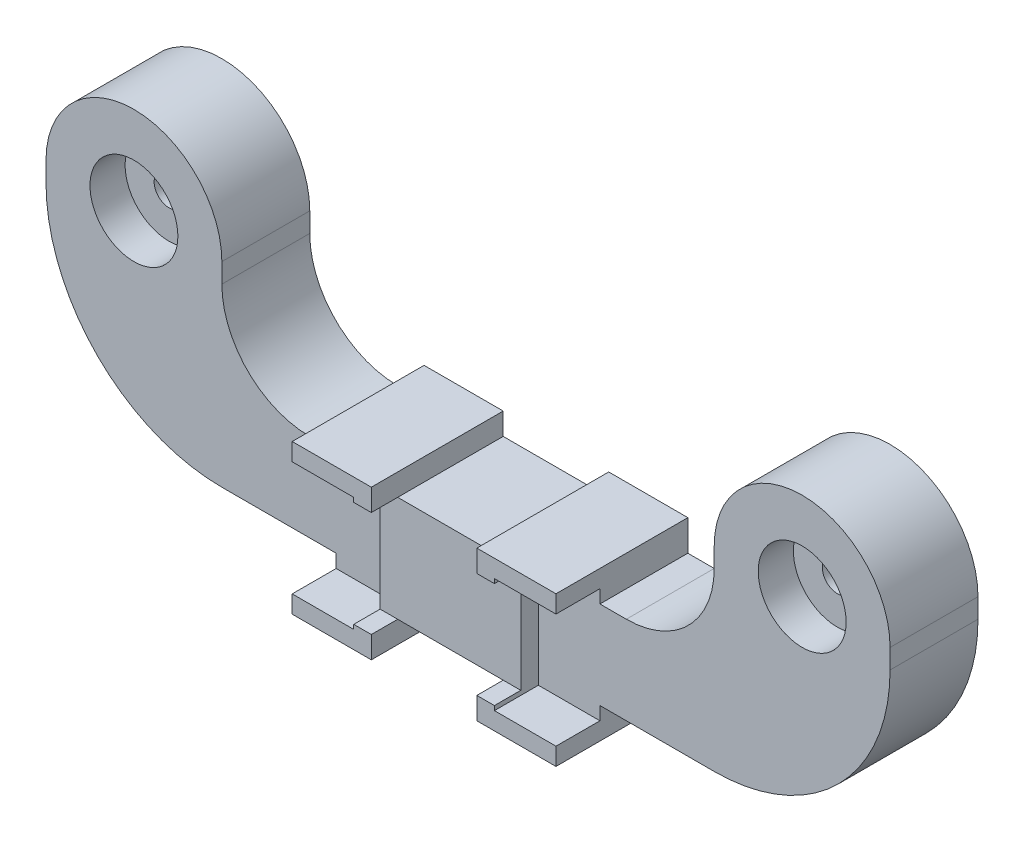
SolidWorks part; units mm, degrees
material "PETG"
ref_plane "Front Plane" through (0, 0, 0) normal (0, 0, 1) x (1, 0, 0)
ref_plane "Top Plane" through (0, 0, 0) normal (0, 1, 0) x (1, 0, 0)
ref_plane "Right Plane" through (0, 0, 0) normal (1, 0, 0) x (0, 0, -1)
sketch "Sketch1" plane through (0, 0, 0) normal (0, 0, 1) x (1, 0, 0)
  line L0 (-48, 20) -> (-48, 22.22)
  line L1 (28, 0) -> (-28, 0)
  line L2 (0, 0) -> (0, 10)
  line L3 (18, 10) -> (-18, 10)
  line L5 (0, 0.8051) -> (0, 50000.8051) construction
  line L6 (-28, 22.22) -> (-28, 20)
  line L7 (28, 22.22) -> (28, 20)
  line L8 (48, 20) -> (48, 22.22)
  circle A0 centre (-38, 22.22) radius 1.7
  arc A1 (-28, 22.22) -> (-48, 22.22) centre (-38, 22.22) ccw
  arc A2 (-18, 10) -> (-28, 20) centre (-18, 20) cw
  arc A3 (-28, 0) -> (-48, 20) centre (-28, 20) cw
  arc A4 (28, 0) -> (48, 20) centre (28, 20) ccw
  arc A5 (18, 10) -> (28, 20) centre (18, 20) ccw
  arc A6 (28, 22.22) -> (48, 22.22) centre (38, 22.22) cw
  circle A7 centre (38, 22.22) radius 1.7
  circle A8 centre (-38, 22.22) radius 5
  circle A9 centre (38, 22.22) radius 5
  dimension "D1" = 38
  dimension "D2" = 3.4
  dimension "D5" = 20
  dimension "D7" = 10
  dimension "D8" = 20
  dimension "D6" = 10
  dimension "D3" = 22.22
  dimension "D4" = 10
extrude "Boss-Extrude1" add sketch "Sketch1" against normal blind 10 contours A3 L1 L2 L3 A2 L6 A1 L0 A8 | A8 A0 | A6 L7 A5 L3 L2 L1 A4 L8 A9 | A9 A7 region at (-27.9027, 11.6824, 0) region at (27.9027, 11.6824, 0) region at (-42.8586, 22.22, 0) region at (33.1414, 22.22, 0)
extrude "Cut-Extrude1" cut sketch "Sketch1<4>" against normal blind 4 contours A8 A0 | A9 A7 region at (-42.8586, 22.22, 0) region at (33.1414, 22.22, 0)
sketch "Sketch1<4>" plane through (0, 0, 0) normal (0, 0, 1) x (1, 0, 0) same geometry as "Sketch1"
sketch "Sketch3" plane through (0, 0, 0) normal (0, 0, 1) x (1, 0, 0)
  line L0 (-6, 11.005) -> (-6, -3.505)
  line L5 (-15, 11.505) -> (-8, 11.505)
  line L6 (-15, 11.505) -> (-15, -1.505)
  line L7 (-15, -1.505) -> (-8, -1.505)
  line L8 (-8, 11.505) -> (-8, -1.505)
  line L10 (-15, 11.505) -> (-15, 13.505)
  line L11 (-15, 13.505) -> (-6, 13.505)
  line L12 (-6, 11.005) -> (-6, 13.505)
  line L14 (-15, -1.505) -> (-15, -3.505)
  line L15 (-15, -3.505) -> (-6, -3.505)
  line L17 (-6, -1.005) -> (-8, -1.005)
  line L18 (-6, 11.005) -> (6, 11.005)
  line L19 (-6, 11.005) -> (-6, -1.005)
  line L20 (-6, -1.005) -> (6, -1.005)
  line L21 (0, 11.005) -> (0, -1.005)
  line L22 (0, 0) -> (0, 50000) construction
  line L23 (-6, 11.005) -> (-8, 11.005)
  line L24 (28, 0) -> (-28, 0) construction
  line L25 (6, 11.005) -> (8, 11.005)
  line L26 (6, 11.005) -> (6, -1.005)
  line L27 (6, -1.005) -> (8, -1.005)
  line L28 (15, -3.505) -> (6, -3.505)
  line L29 (15, -1.505) -> (15, -3.505)
  line L30 (6, 11.005) -> (6, 13.505)
  line L31 (15, 13.505) -> (6, 13.505)
  line L32 (15, 11.505) -> (15, 13.505)
  line L33 (8, 11.505) -> (8, -1.505)
  line L34 (15, -1.505) -> (8, -1.505)
  line L35 (15, 11.505) -> (15, -1.505)
  line L36 (15, 11.505) -> (8, 11.505)
  line L37 (6, 11.005) -> (6, -3.505)
  point P13 (0, 5)
  point P20 (0, 0)
  line M5 (-28, 0) -> (28, 0)
  line M11 (18, 10) -> (-18, 10)
  dimension "D1" = 15
  dimension "D2" = 13.01
  dimension "D3" = 5
  dimension "D4" = 2
  dimension "D5" = 0.5
  dimension "D6" = 0.5
  dimension "D7" = 7
extrude "Boss-Extrude2" add sketch "Sketch3" against normal through all contours L21 L18 L0 M11 | L26 L18 L21 M11 | L21 L0 L20 M5 | L26 L21 L20 M5 | L0 L23 L8 M11 | L8 L5 L6 M11 | L23 L12 L11 L10 L5 L8 | L0 L17 L8 L7 L14 L15 | L17 L0 L8 M5 | L33 L26 L27 M5 | L27 L37 L28 L29 L34 L33 | L35 L33 L34 M5 | L35 L36 L33 M11 | L33 L25 L26 M11 | L36 L32 L31 L30 L25 L33 | L8 L6 L7 M5 region at (-7, -0.5025, 0) region at (-10.3158, -2.4392, 0) region at (-3, -0.5025, 0) region at (-11.5, -0.7525, 0) region at (3, -0.5025, 0) region at (-7, 10.5025, 0) region at (-3, 10.5025, 0) region at (7, -0.5025, 0) region at (10.3158, -2.4392, 0) region at (-10.3158, 12.4392, 0) region at (3, 10.5025, 0) region at (-11.5, 10.7525, 0) region at (11.5, -0.7525, 0) region at (7, 10.5025, 0) region at (10.3158, 12.4392, 0) region at (11.5, 10.7525, 0)
extrude "Boss-Extrude3" add sketch "Sketch3<3>" along normal blind 5 contours L23 L12 L11 L10 L5 L8 | L0 L17 L8 L7 L14 L15 | L27 L37 L28 L29 L34 L33 | L36 L32 L31 L30 L25 L33 region at (-10.3158, 12.4392, 0) region at (-10.3158, -2.4392, 0) region at (10.3158, 12.4392, 0) region at (10.3158, -2.4392, 0)
sketch "Sketch3<3>" plane through (0, 0, 0) normal (0, 0, 1) x (1, 0, 0) same geometry as "Sketch3"
extrude "Boss-Extrude4" add sketch "Sketch3<4>" along normal blind 2 contours L8 L0 M11 M5 | L21 L0 M11 M5 | L33 L26 M11 M5 | L26 L21 M11 M5 | L26 L18 L21 M11 | L33 L25 L26 M11 | L21 L18 L0 M11 | L0 L23 L8 M11 | L17 L0 L8 M5 | L21 L0 L20 M5 | L26 L21 L20 M5 | L33 L26 L27 M5 region at (-7, -0.5025, 0) region at (-3, -0.5025, 0) region at (-7, 5, 0) region at (-3, 5, 0) region at (3, -0.5025, 0) region at (-7, 10.5025, 0) region at (-3, 10.5025, 0) region at (3, 5, 0) region at (7, -0.5025, 0) region at (3, 10.5025, 0) region at (7, 5, 0) region at (7, 10.5025, 0)
sketch "Sketch3<4>" plane through (0, 0, 0) normal (0, 0, 1) x (1, 0, 0) same geometry as "Sketch3"
equation "\"tol_dia_id_intfc\" = 0.0200mm ' For hole diameters - Interference fit"
equation "\"tol_dia_id_slip\"  = 0.0300mm ' For hole diameters - Slip fit"
equation "\"tol_dia_id_clear\" = 0.0500mm ' For hole diameters - Clearance fit"
equation "\"tol_dia_od_intfc\" = 0.0200mm ' For shaft diameters - Interference fit"
equation "\"tol_dia_od_slip\"  = 0.0300mm ' For shaft diameters - Slip fit"
equation "\"tol_dia_od_clear\" = 0.0500mm ' For shaft diameters - Clearance fit"
equation "\"tol_general_intfc\"= 0.0030mm ' For general parts (Horiz) - Interference fit"
equation "\"tol_general_slip\" = 0.0050mm ' For general parts (Horiz) - Slip fit"
equation "\"tol_general_clear\"= 0.0100mm ' For general parts (Horiz) - Clearance fit"
equation "\"tol_layer_intfc\"  = 0.0030mm ' For all parts (Vert) - Interference fit"
equation "\"tol_layer_slip\"   = 0.0050mm ' For all parts (Vert) - Slip fit"
equation "\"tol_layer_clear\"  = 0.0100mm ' For all parts (Vert) - Clearance fit"
equation "\"tol_corner_rad\"   = 0.100mm ' For corners that fit into other parts"
equation "\"D2@Sketch3\"=13mm+\"tol_general_slip\"*2"
equation "\"D6@Sketch3\"=\"D5@Sketch3\""
